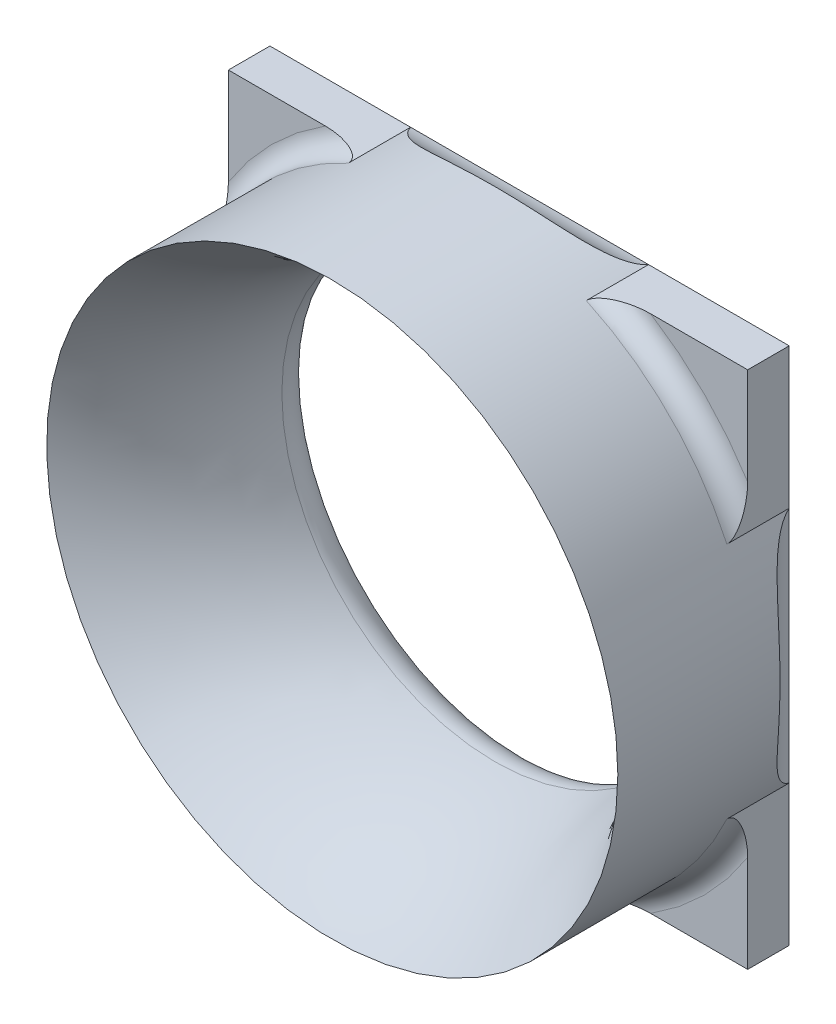
SolidWorks part; units mm, degrees
ref_plane "Ebene vorne" through (0, 0, 0) normal (0, 0, 1) x (1, 0, 0)
ref_plane "Ebene oben" through (0, 0, 0) normal (0, 1, 0) x (1, 0, 0)
ref_plane "Ebene rechts" through (0, 0, 0) normal (1, 0, 0) x (0, 0, -1)
sketch "Skizze1" plane through (0, 0, 0) normal (0, 0, 1) x (1, 0, 0)
  line L1 (-25, -25) -> (25, -25)
  line L2 (-25, -25) -> (-25, 25)
  line L3 (-25, 25) -> (25, 25)
  line L4 (25, -25) -> (25, 25)
  line L5 (-25, -25) -> (25, 25) construction
  line L6 (-25, 25) -> (25, -25) construction
  circle A0 centre (0, 0) radius 20.33
  dimension "D3" = 40.66
  dimension "D1" = 50
  dimension "D2" = 50
extrude "Aufsatz-Linear austragen1" add sketch "Skizze1" along normal blind 4
sketch "Skizze2" plane through (0, 0, 4) normal (0, 0, 1) x (1, 0, 0)
  circle A0 centre (0, 0) radius 20.33
  circle A1 centre (0, 0) radius 27.5
  dimension "D1" = 40.66
  dimension "D2" = 55
extrude "Aufsatz-Linear austragen2" add sketch "Skizze2" along normal blind 15
fillet "Verrundung1" radius 5 4 edges at (-25, 0, 4) (25, 0, 4) (0, -25, 4) (0, 25, 4)
fillet "Verrundung2" radius 2 4 edges at (-19.4454, -19.4454, 4) (19.4454, -19.4454, 4) (19.4454, 19.4454, 4) (-19.4454, 19.4454, 4)
fillet "Verrundung3" radius 28.5 1 edges at (20.33, 0, 19)
fillet "Verrundung4" radius 3 1 edges at (20.33, 0, 0)
